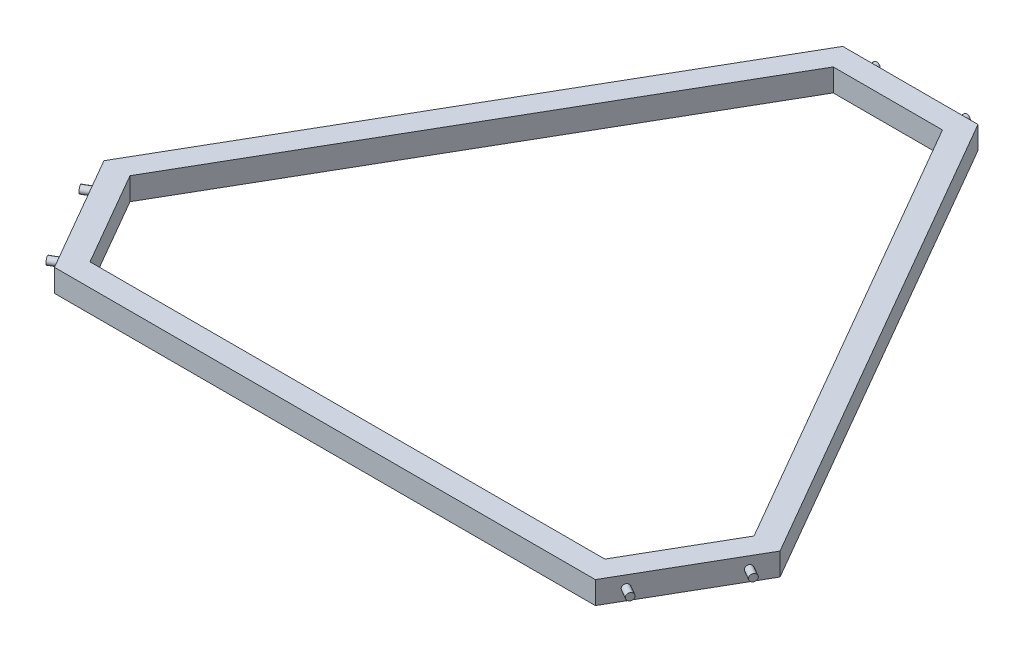
SolidWorks part; units mm, degrees
ref_plane "Front Plane" through (0, 0, 0) normal (0, 0, 1) x (1, 0, 0)
ref_plane "Top Plane" through (0, 0, 0) normal (0, 1, 0) x (1, 0, 0)
ref_plane "Right Plane" through (0, 0, 0) normal (1, 0, 0) x (0, 0, -1)
sketch "Sketch1" plane through (0, 0, 0) normal (0, 1, 0) x (1, 0, 0)
  line L0 (-600, -519.6152) -> (600, -519.6152)
  line L1 (600, -519.6152) -> (750, -259.8076)
  line L2 (750, -259.8076) -> (150, 779.4229)
  line L3 (150, 779.4229) -> (-150, 779.4229)
  line L4 (-150, 779.4229) -> (-750, -259.8076)
  line L5 (-750, -259.8076) -> (-600, -519.6152)
  line L6 (-121.1325, 729.4229) -> (-692.265, -259.8076)
  line L7 (-692.265, -259.8076) -> (-571.1325, -469.6152)
  line L8 (-571.1325, -469.6152) -> (571.1325, -469.6152)
  line L9 (571.1325, -469.6152) -> (692.265, -259.8076)
  line L10 (692.265, -259.8076) -> (121.1325, 729.4229)
  line L11 (121.1325, 729.4229) -> (-121.1325, 729.4229)
  line L12 (0, -519.6152) -> (0, 843.7812) construction
  line L13 (406.6987, 234.8076) -> (-265.2767, -153.1576) construction
  dimension "D1" = 1200
  dimension "D2" = 60
  dimension "D3" = 300
  dimension "D4" = 120
  dimension "D5" = 50
extrude "Boss-Extrude1" add sketch "Sketch1" along normal blind 50
sketch "Sketch2" plane through (675, 0, 389.7114) normal (0.866, 0, 0.5) x (0.5, 0, -0.866)
  line L0 (-150, 25) -> (150, 25) construction
  line L1 (-150, 50) -> (-150, 0) construction
  line L2 (150, 50) -> (150, 0) construction
  line L3 (0, 50) -> (0, 0) construction
  line L4 (-150, 50) -> (150, 50) construction
  line L5 (-150, 0) -> (150, 0) construction
  circle A0 centre (-100, 25) radius 8
  circle A1 centre (100, 25) radius 8
  dimension "D1" = 16
  dimension "D2" = 50
extrude "Boss-Extrude2" add sketch "Sketch2" along normal blind 25
ref_axis "Axis1" through (0, 52.5, 0) along (0, -1, 0)
pattern_circular "CirPattern1" count 3 over 360 about axis through (0, 52.5, 0) along (0, -1, 0) of "Boss-Extrude2"
